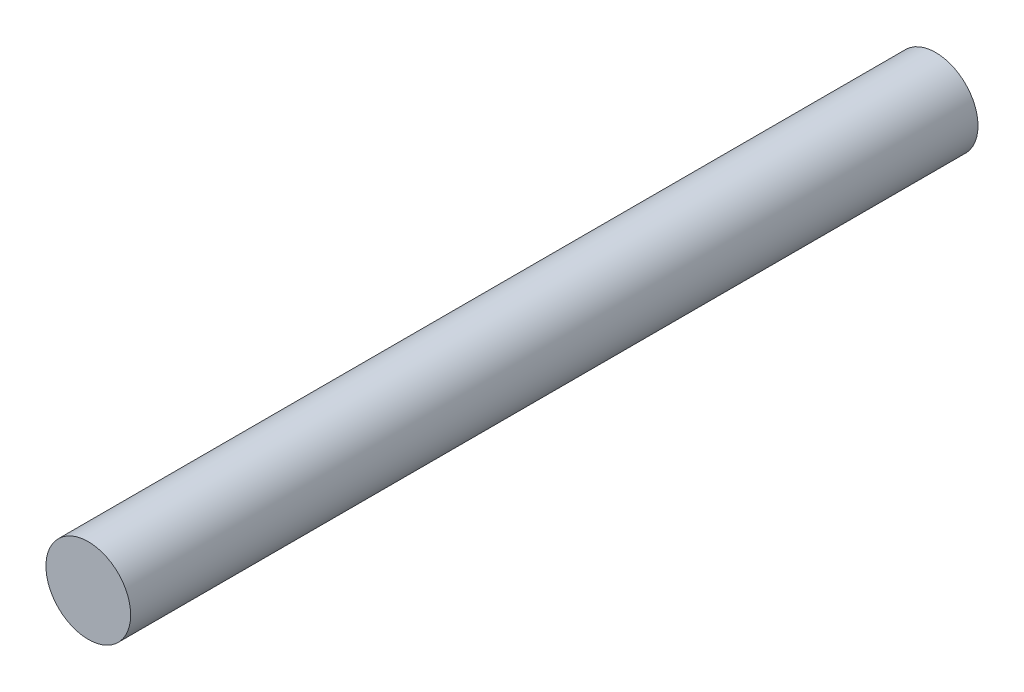
SolidWorks part; units mm, degrees
ref_plane "Front Plane" through (0, 0, 0) normal (0, 0, 1) x (1, 0, 0)
ref_plane "Top Plane" through (0, 0, 0) normal (0, 1, 0) x (1, 0, 0)
ref_plane "Right Plane" through (0, 0, 0) normal (1, 0, 0) x (0, 0, -1)
sketch "Sketch1" plane through (0, 0, 0) normal (0, 0, 1) x (1, 0, 0)
  circle A0 centre (0, 0) radius 6.35
extrude "Boss-Extrude1" add sketch "Sketch1" along normal blind 127
